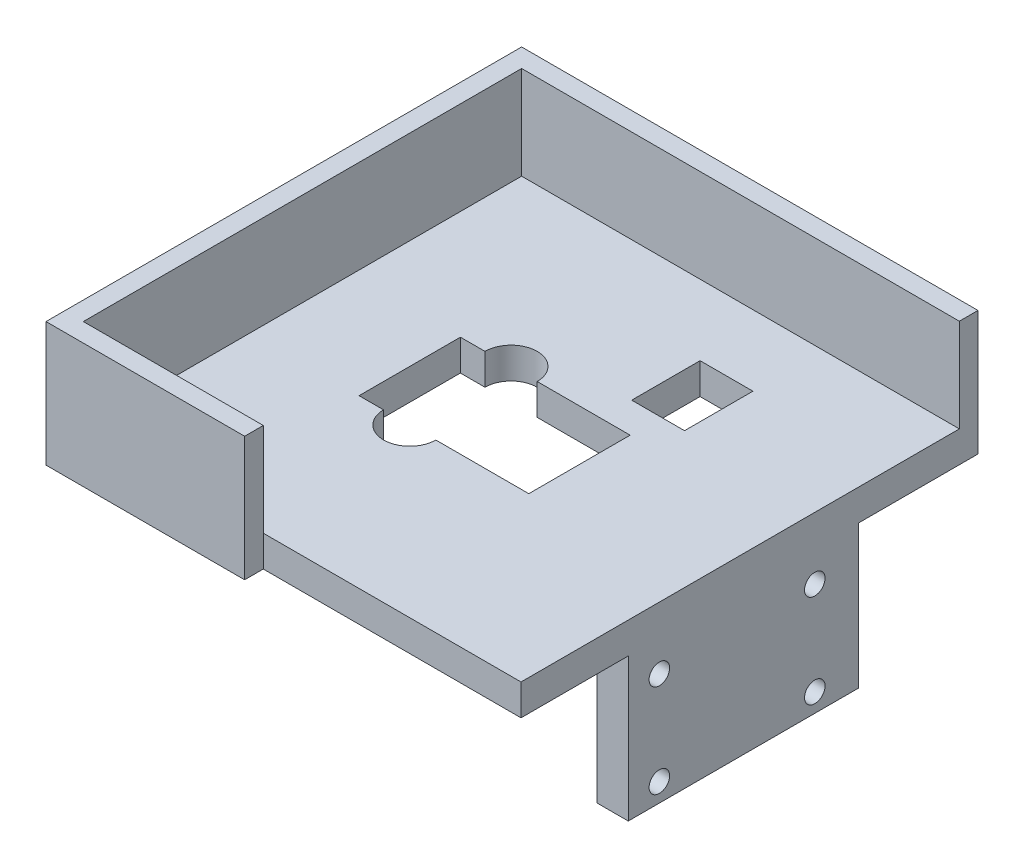
SolidWorks part; units mm, degrees
ref_plane "前视基准面" through (0, 0, 0) normal (0, 0, 1) x (1, 0, 0)
ref_plane "上视基准面" through (0, 0, 0) normal (0, 1, 0) x (1, 0, 0)
ref_plane "右视基准面" through (0, 0, 0) normal (1, 0, 0) x (0, 0, -1)
other "Configuration Table"
sketch "草图1" plane through (0, 0, 0) normal (0, 1, 0) x (1, 0, 0)
  line L1 (0, 0) -> (55, 0)
  line L2 (0, 0) -> (0, -70)
  line L3 (0, -70) -> (55, -70)
  line L4 (55, 0) -> (55, -70)
  dimension "D1" = 55
  dimension "D2" = 70
extrude "凸台-拉伸1" add sketch "草图1" along normal blind 5
sketch "草图2" plane through (55, 0, 0) normal (1, 0, 0) x (0, 0, -1)
  line L0 (0, 5) -> (0, 0) construction
  line L1 (0, 5) -> (-37, 5)
  line L2 (0, 5) -> (0, -23)
  line L3 (0, -23) -> (-37, -23)
  line L4 (-37, 5) -> (-37, -23)
  line L5 (-70, 5) -> (0, 5) construction
  dimension "D1" = 37
  dimension "D2" = 28
extrude "凸台-拉伸2" add sketch "草图2" against normal blind 5
sketch "草图3" plane through (55, 0, 0) normal (1, 0, 0) x (0, 0, -1)
  line L0 (-37, -23) -> (0, -23) construction
  line L2 (0, 5) -> (0, -23) construction
  circle A0 centre (-7, -5) radius 1.65
  circle A1 centre (-32, -5) radius 1.65
  circle A2 centre (-32, -20) radius 1.65
  circle A3 centre (-7, -20) radius 1.65
  dimension "D1" = 15
  dimension "D3" = 3.3
  dimension "D4" = 3.3
  dimension "D5" = 3.3
  dimension "D6" = 3.3
  dimension "D7" = 3
  dimension "D8" = 7
  dimension "D2" = 25
extrude "切除-拉伸1" cut sketch "草图3" against normal blind 5
sketch "草图4" plane through (0, 5, 0) normal (0, 1, 0) x (1, 0, 0)
  line L0 (55, 0) -> (0, 0) construction
  circle A0 centre (25.9415, -19.25) radius 3.6614
  dimension "D1" = 19.25
sketch "草图5" plane through (0, 5, 0) normal (0, 1, 0) x (1, 0, 0)
  line L1 (0, 0) -> (55, 0)
  line L2 (0, 0) -> (0, 15.75)
  line L3 (0, 15.75) -> (55, 15.75)
  line L4 (55, 0) -> (55, 15.75)
  circle A0 centre (25.9415, -19.25) radius 3.6614 construction
  dimension "D1" = 55
  dimension "D2" = 35
extrude "凸台-拉伸3" add sketch "草图5" against normal blind 5
sketch "草图6" plane through (0, 5, 0) normal (0, 1, 0) x (1, 0, 0)
  line L0 (0, 15.75) -> (0, -70) construction
  line L1 (0, -54.25) -> (55, -54.25)
  line L2 (0, -54.25) -> (0, -70)
  line L3 (0, -70) -> (55, -70)
  line L4 (55, -54.25) -> (55, -70)
  circle A0 centre (25.9415, -19.25) radius 3.6614 construction
  dimension "D1" = 35
extrude "切除-拉伸2" cut sketch "草图6" against normal blind 5
sketch "草图8" plane through (0, 5, 0) normal (0, 1, 0) x (1, 0, 0)
  line L0 (55, -54.25) -> (55, 15.75) construction
  line L2 (18.4, -11.1) -> (29.4, -11.1)
  line L3 (2.1, -27.4) -> (6.05, -27.4)
  line L4 (2.1, -27.4) -> (2.1, -11.1)
  line L5 (2.1, -11.1) -> (6.05, -11.1)
  line L7 (2.1, -27.4) -> (18.4, -11.1) construction
  line L8 (2.1, -11.1) -> (18.4, -27.4) construction
  line L9 (29.4, -11.1) -> (29.4, -27.4)
  line L10 (29.4, -27.4) -> (18.4, -27.4)
  line L11 (14.45, -11.1) -> (18.4, -11.1)
  line L12 (14.45, -27.4) -> (18.4, -27.4)
  arc A1 (6.05, -11.1) -> (14.45, -11.1) centre (10.25, -11.1) cw
  arc A2 (6.05, -27.4) -> (14.45, -27.4) centre (10.25, -27.4) ccw
  point P0 (10.25, -19.25)
  dimension "D1" = 44.75
  dimension "D2" = 4.2
  dimension "D6" = 4.2
  dimension "D3" = 16.3
  dimension "D4" = 16.3
  dimension "D5" = 11
extrude "切除-拉伸3" cut sketch "草图8" against normal blind 5
sketch "草图9" plane through (0, 5, 0) normal (0, 1, 0) x (1, 0, 0)
  line L0 (29.4, -11.1) -> (14.45, -11.1) construction
  line L1 (24.65, 4.9) -> (33.15, 4.9)
  line L2 (24.65, 4.9) -> (24.65, -6.1)
  line L3 (24.65, -6.1) -> (33.15, -6.1)
  line L4 (33.15, 4.9) -> (33.15, -6.1)
  line L5 (29.4, -27.4) -> (29.4, -11.1) construction
  dimension "D1" = 11
  dimension "D2" = 5
  dimension "D3" = 8.5
  dimension "D4" = 3.75
extrude "切除-拉伸4" cut sketch "草图9" against normal blind 8
sketch "草图10" plane through (0, 0, -15.75) normal (0, 0, -1) x (-1, 0, 0)
  line L0 (-55, 0) -> (0, 0) construction
  line L1 (-55, 0) -> (0, 0)
  line L2 (-55, 0) -> (-55, 10)
  line L3 (-55, 10) -> (0, 10)
  line L4 (0, 0) -> (0, 10)
  line L5 (-55, 0) -> (-55, 5) construction
  dimension "D1" = 10
  dimension "D2" = 55
sketch "草图11" plane through (0, 5, 0) normal (0, 1, 0) x (1, 0, 0)
  line L0 (2.1, -11.1) -> (2.1, -27.4) construction
  line L1 (0, 15.75) -> (-15.4, 15.75)
  line L2 (0, 15.75) -> (0, -54.25)
  line L3 (0, -54.25) -> (-15.4, -54.25)
  line L4 (-15.4, 15.75) -> (-15.4, -54.25)
  dimension "D1" = 17.5
extrude "凸台-拉伸4" add sketch "草图11" against normal blind 5
sketch "草图12" plane through (0, 5, 0) normal (0, 1, 0) x (1, 0, 0)
  line L0 (55, -54.25) -> (55, 15.75) construction
  line L1 (-15.4, 15.75) -> (55, 15.75)
  line L2 (-15.4, 15.75) -> (-15.4, 16.25)
  line L3 (-15.4, 16.25) -> (55, 16.25)
  line L4 (55, 15.75) -> (55, 16.25)
  dimension "D1" = 0.5
extrude "凸台-拉伸5" add sketch "草图12" against normal blind 5
sketch "草图14" plane through (0, 0, -16.25) normal (0, 0, -1) x (-1, 0, 0)
  line L0 (-55, 0) -> (-55, 5) construction
  line L1 (-55, 0) -> (15.4, 0)
  line L2 (-55, 0) -> (-55, 20)
  line L3 (-55, 20) -> (15.4, 20)
  line L4 (15.4, 0) -> (15.4, 20)
  line L5 (-55, 0) -> (15.4, 0) construction
  line L6 (15.4, 0) -> (15.4, 5) construction
  dimension "D1" = 20
extrude "凸台-拉伸6" add sketch "草图14" along normal blind 3
sketch "草图15" plane through (0, 0, 54.25) normal (0, 0, 1) x (1, 0, 0)
  line L0 (-15.4, 20) -> (55, 20) construction
  line L1 (-15.4, 0) -> (13.5464, 0)
  line L2 (-15.4, 0) -> (-15.4, 20)
  line L3 (-15.4, 20) -> (13.5464, 20)
  line L4 (13.5464, 0) -> (13.5464, 20)
extrude "凸台-拉伸7" add sketch "草图15" along normal blind 3
sketch "草图16" plane through (-15.4, 0, 0) normal (-1, 0, 0) x (0, 0, 1)
  line L0 (-19.25, 0) -> (57.25, 0) construction
  line L1 (-19.25, 0) -> (57.25, 0)
  line L2 (-19.25, 0) -> (-19.25, 20)
  line L3 (-19.25, 20) -> (57.25, 20)
  line L4 (57.25, 0) -> (57.25, 20)
  line L5 (-19.25, 0) -> (-19.25, 20) construction
extrude "凸台-拉伸8" add sketch "草图16" along normal blind 3
ref_plane "基准面1" through (0, 0, 20) normal (0, 0, 1) x (1, 0, 0)
sketch "草图17" plane through (0, 0, 20) normal (0, 0, 1) x (1, 0, 0)
  line L0 (31.2849, 1.0755) -> (51.5034, -12.4186)
  line L1 (51.5034, -12.4186) -> (53.209, 1.0755)
  line L2 (53.209, 1.0755) -> (31.2849, 1.0755)
extrude "凸台-拉伸9" add sketch "草图17" against normal mid plane 12
